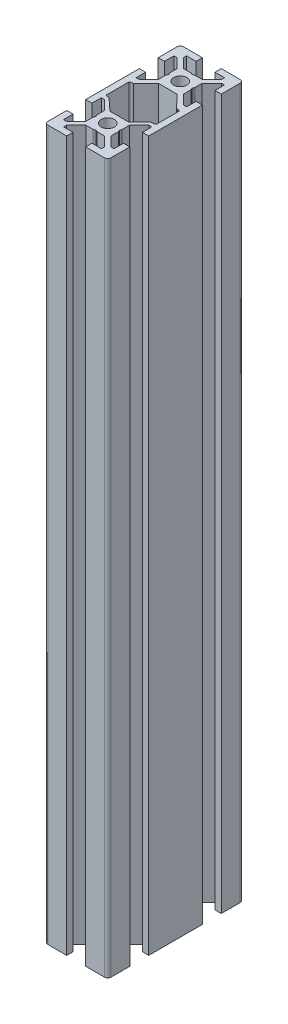
SolidWorks part; units mm, degrees
material "6063-T5"
ref_plane "Top Plane" through (0, 0, 0) normal (0, 0, 1) x (1, 0, 0)
ref_plane "Front Plane" through (0, 0, 0) normal (0, 1, 0) x (1, 0, 0)
ref_plane "Side Plane" through (0, 0, 0) normal (1, 0, 0) x (0, 0, -1)
sketch "Sketch3" plane through (0, 0, 0) normal (0, 1, 0) x (1, 0, 0)
  line L0 (-13.8894, 24) -> (-15.1622, 23.8)
  line L1 (-15.7622, 23.6) -> (-15.7622, 9.279)
  line L2 (-15.1622, 8.679) -> (-13.8894, 8.679)
  line L3 (-13.4651, 8.5033) -> (-5.6408, 1.321)
  line L4 (-5.6408, 1.321) -> (6.0854, 1.321)
  line L5 (6.0854, 1.321) -> (12.9275, 8.3595)
  line L6 (15.1167, 8.3595) -> (15.3559, 8.3717)
  line L7 (16.2378, 9.279) -> (16.2067, 23.6)
  line L8 (16.2067, 23.6) -> (14.3651, 24)
  line L9 (13.9408, 24) -> (6.1165, 32)
  line L10 (-5.6408, 32) -> (-13.4651, 24)
  line L11 (6.1165, 32) -> (-5.6408, 32)
  line L12 (-19.7933, 34.0345) -> (-19.7933, 0.0345)
  line L13 (-19.7933, 0.0345) -> (-15.7933, 0.0345)
  line L14 (-15.7933, 0.0345) -> (-15.7933, 6.0345)
  line L15 (-15.7933, 6.0345) -> (-13.9146, 6.0345)
  line L16 (-13.9146, 6.0345) -> (-7.7933, -0.0869)
  line L17 (-7.7933, -0.0869) -> (-7.7933, -0.9655)
  line L18 (-7.7933, -0.9655) -> (-7.7933, -4.6584)
  line L20 (-7.6593, -5.1584) -> (-7.1933, -5.9655)
  line L21 (-7.1933, -5.9655) -> (-7.6593, -6.7727)
  line L22 (-7.7933, -7.2727) -> (-7.7933, -11.8442)
  line L23 (-7.7933, -11.8442) -> (-13.9146, -17.9655)
  line L24 (-13.9146, -17.9655) -> (-15.7933, -17.9655)
  line L25 (-15.7933, -17.9655) -> (-15.7933, -11.9655)
  line L26 (-15.7933, -11.9655) -> (-19.7933, -11.9655)
  line L27 (-19.7933, -11.9655) -> (-19.7933, -23.9655)
  line L28 (-17.7933, -25.9655) -> (-5.7933, -25.9655)
  line L29 (-5.7933, -25.9655) -> (-5.7933, -21.9655)
  line L30 (-5.7933, -21.9655) -> (-11.7933, -21.9655)
  line L31 (-11.7933, -21.9655) -> (-11.7933, -20.0869)
  line L32 (-11.7933, -20.0869) -> (-5.672, -13.9655)
  line L33 (-5.672, -13.9655) -> (-4.7933, -13.9655)
  line L34 (-4.7933, -13.9655) -> (-1.1005, -13.9655)
  line L36 (-0.6005, -13.8316) -> (0.2067, -13.3655)
  line L37 (0.2067, -13.3655) -> (1.0139, -13.8316)
  line L38 (1.5139, -13.9655) -> (6.0854, -13.9655)
  line L39 (6.0854, -13.9655) -> (12.2067, -20.0869)
  line L40 (12.2067, -20.0869) -> (12.2067, -21.9655)
  line L41 (12.2067, -21.9655) -> (6.2067, -21.9655)
  line L42 (6.2067, -21.9655) -> (6.2067, -25.9655)
  line L43 (6.2067, -25.9655) -> (18.2067, -25.9655)
  line L44 (20.2067, -23.9655) -> (20.2067, -11.9655)
  line L45 (20.2067, -11.9655) -> (16.2067, -11.9655)
  line L46 (16.2067, -11.9655) -> (16.2067, -17.9655)
  line L47 (16.2067, -17.9655) -> (14.328, -17.9655)
  line L48 (14.328, -17.9655) -> (8.2067, -11.8442)
  line L49 (8.2067, -11.8442) -> (8.2067, -10.9655)
  line L50 (8.2067, -10.9655) -> (8.2067, -7.2727)
  line L52 (8.0727, -6.7727) -> (7.6067, -5.9655)
  line L53 (7.6067, -5.9655) -> (8.0727, -5.1584)
  line L54 (8.2067, -4.6584) -> (8.2067, -0.0869)
  line L55 (8.2067, -0.0869) -> (14.328, 6.0345)
  line L56 (14.328, 6.0345) -> (16.2067, 6.0345)
  line L57 (16.2067, 6.0345) -> (16.2067, 0.0345)
  line L58 (16.2067, 0.0345) -> (20.2067, 0.0345)
  line L59 (20.2067, 0.0345) -> (20.2067, 34.0345)
  line L60 (20.2067, 34.0345) -> (16.2067, 34.0345)
  line L61 (16.2067, 34.0345) -> (16.2067, 28.0345)
  line L62 (16.2067, 28.0345) -> (14.328, 28.0345)
  line L63 (14.328, 28.0345) -> (8.2067, 34.1558)
  line L64 (8.2067, 34.1558) -> (8.2067, 38.7273)
  line L65 (8.0727, 39.2273) -> (7.6067, 40.0345)
  line L66 (7.6067, 40.0345) -> (8.0727, 40.8416)
  line L68 (8.2067, 41.3416) -> (8.2067, 45.0345)
  line L69 (8.2067, 45.0345) -> (8.2067, 45.9131)
  line L70 (8.2067, 45.9131) -> (14.328, 52.0345)
  line L71 (14.328, 52.0345) -> (16.2067, 52.0345)
  line L72 (16.2067, 52.0345) -> (16.2067, 46.0345)
  line L73 (16.2067, 46.0345) -> (20.2067, 46.0345)
  line L74 (20.2067, 46.0345) -> (20.2067, 58.0345)
  line L75 (18.2067, 60.0345) -> (6.2067, 60.0345)
  line L76 (6.2067, 60.0345) -> (6.2067, 56.0345)
  line L77 (6.2067, 56.0345) -> (12.2067, 56.0345)
  line L78 (12.2067, 56.0345) -> (12.2067, 54.1558)
  line L79 (12.2067, 54.1558) -> (6.0854, 48.0345)
  line L80 (6.0854, 48.0345) -> (1.5139, 48.0345)
  line L81 (1.0139, 47.9005) -> (0.2067, 47.4345)
  line L82 (0.2067, 47.4345) -> (-0.6005, 47.9005)
  line L84 (-1.1005, 48.0345) -> (-4.7933, 48.0345)
  line L85 (-4.7933, 48.0345) -> (-5.672, 48.0345)
  line L86 (-5.672, 48.0345) -> (-11.7933, 54.1558)
  line L87 (-11.7933, 54.1558) -> (-11.7933, 56.0345)
  line L88 (-11.7933, 56.0345) -> (-5.7933, 56.0345)
  line L89 (-5.7933, 56.0345) -> (-5.7933, 60.0345)
  line L90 (-5.7933, 60.0345) -> (-17.7933, 60.0345)
  line L91 (-19.7933, 58.0345) -> (-19.7933, 46.0345)
  line L92 (-19.7933, 46.0345) -> (-15.7933, 46.0345)
  line L93 (-15.7933, 46.0345) -> (-15.7933, 52.0345)
  line L94 (-15.7933, 52.0345) -> (-13.9146, 52.0345)
  line L95 (-13.9146, 52.0345) -> (-7.7933, 45.9131)
  line L96 (-7.7933, 45.9131) -> (-7.7933, 41.3416)
  line L97 (-7.6593, 40.8416) -> (-7.1933, 40.0345)
  line L98 (-7.1933, 40.0345) -> (-7.6593, 39.2273)
  line L100 (-7.7933, 38.7273) -> (-7.7933, 35.0345)
  line L101 (-7.7933, 35.0345) -> (-7.7933, 34.1558)
  line L102 (-7.7933, 34.1558) -> (-13.9146, 28.0345)
  line L103 (-13.9146, 28.0345) -> (-15.7933, 28.0345)
  line L104 (-15.7933, 28.0345) -> (-15.7933, 34.0345)
  line L105 (-15.7933, 34.0345) -> (-19.7933, 34.0345)
  line L106 (15.3559, 8.3717) -> (16.2378, 9.279)
  line L109 (-15.1622, 8.679) -> (-15.7622, 9.279)
  line L112 (12.9275, 8.3595) -> (15.1167, 8.3595)
  arc A0 (-3.9796, -5.9655) -> (4.4204, -5.9655) centre (0.2204, -5.9655) ccw
  arc A1 (4.4204, -5.9655) -> (-3.9796, -5.9655) centre (0.2204, -5.9655) ccw
  arc A2 (-15.1622, 23.8) -> (-15.7622, 23.6) centre (-14.4699, 20.7231) ccw
  arc A3 (-13.8894, 24) -> (-13.4651, 24) centre (-13.6772, 27.3395) ccw
  arc A4 (-7.7933, -4.6584) -> (-7.6593, -5.1584) centre (-6.7933, -4.6584) ccw
  arc A5 (-7.6593, -6.7727) -> (-7.7933, -7.2727) centre (-6.7933, -7.2727) ccw
  arc A6 (-19.7933, -23.9655) -> (-17.7933, -25.9655) centre (-17.7933, -23.9655) ccw
  arc A7 (-1.1005, -13.9655) -> (-0.6005, -13.8316) centre (-1.1005, -12.9655) ccw
  arc A8 (1.0139, -13.8316) -> (1.5139, -13.9655) centre (1.5139, -12.9655) ccw
  arc A9 (18.2067, -25.9655) -> (20.2067, -23.9655) centre (18.2067, -23.9655) ccw
  arc A10 (8.2067, -7.2727) -> (8.0727, -6.7727) centre (7.2067, -7.2727) ccw
  arc A11 (8.0727, -5.1584) -> (8.2067, -4.6584) centre (7.2067, -4.6584) ccw
  arc A12 (8.2067, 38.7273) -> (8.0727, 39.2273) centre (7.2067, 38.7273) ccw
  arc A13 (8.0727, 40.8416) -> (8.2067, 41.3416) centre (7.2067, 41.3416) ccw
  arc A14 (20.2067, 58.0345) -> (18.2067, 60.0345) centre (18.2067, 58.0345) ccw
  arc A15 (1.5139, 48.0345) -> (1.0139, 47.9005) centre (1.5139, 47.0345) ccw
  arc A16 (-0.6005, 47.9005) -> (-1.1005, 48.0345) centre (-1.1005, 47.0345) ccw
  arc A17 (-17.7933, 60.0345) -> (-19.7933, 58.0345) centre (-17.7933, 58.0345) ccw
  arc A18 (-7.7933, 41.3416) -> (-7.6593, 40.8416) centre (-6.7933, 41.3416) ccw
  arc A19 (-7.6593, 39.2273) -> (-7.7933, 38.7273) centre (-6.7933, 38.7273) ccw
  arc A21 (-13.4651, 8.5033) -> (-13.8894, 8.679) centre (-14.7912, 5.9019) ccw
  arc A25 (13.9408, 24) -> (14.3651, 24) centre (14.1529, 27.3395) ccw
  arc A26 (-3.9933, 40.0345) -> (4.4067, 40.0345) centre (0.2067, 40.0345) ccw
  arc A27 (4.4067, 40.0345) -> (-3.9933, 40.0345) centre (0.2067, 40.0345) ccw
  dimension "D1" = 40
  dimension "D2" = 36
  dimension "D3" = 14
  dimension "D4" = 34
  dimension "D5" = 34
  dimension "D6" = 46
extrude "Boss-Extrude3" add sketch "Sketch3" along normal blind 450
